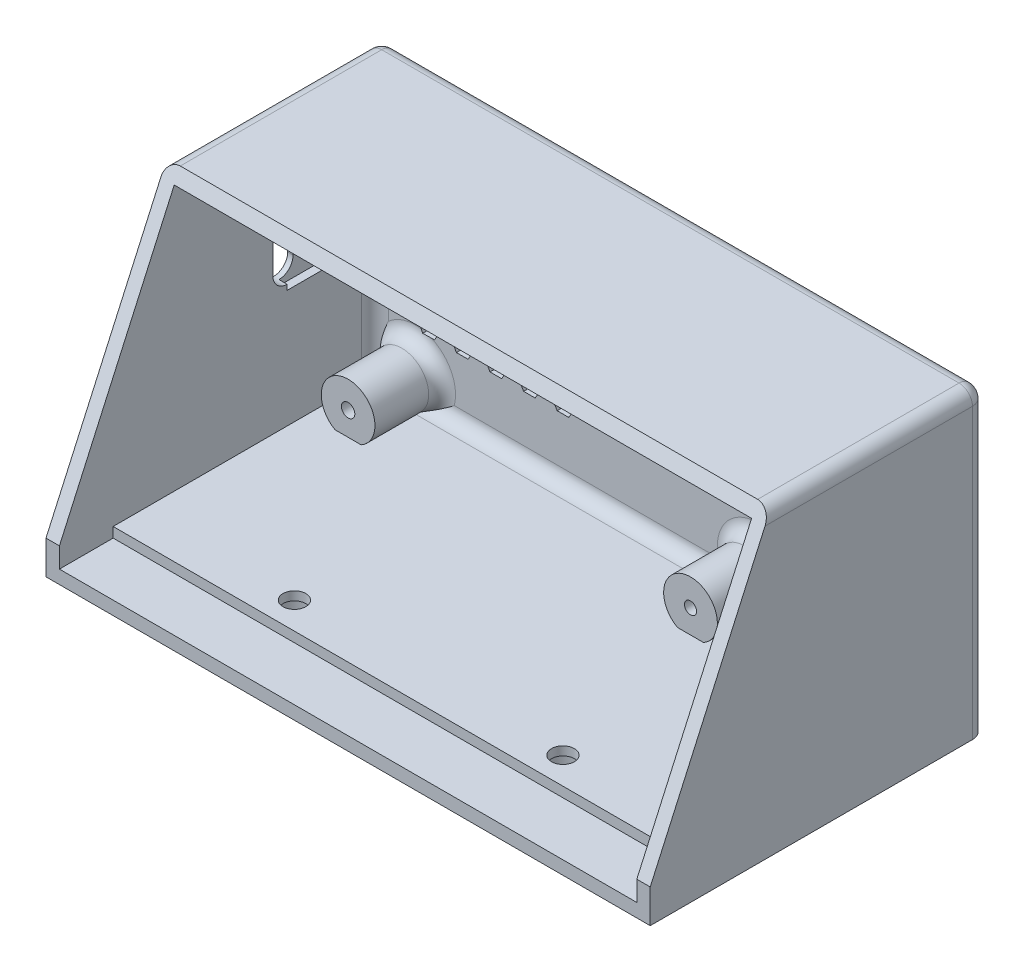
SolidWorks part; units mm, degrees
ref_plane "前视基准面" through (0, 0, 0) normal (0, 0, 1) x (1, 0, 0)
ref_plane "上视基准面" through (0, 0, 0) normal (0, 1, 0) x (1, 0, 0)
ref_plane "右视基准面" through (0, 0, 0) normal (1, 0, 0) x (0, 0, -1)
sketch "草图1" plane through (0, 0, 0) normal (0, 0, 1) x (1, 0, 0)
  line L1 (0, 0) -> (90, 0)
  line L2 (0, 0) -> (0, 45)
  line L3 (0, 45) -> (90, 45)
  line L4 (90, 0) -> (90, 45)
  dimension "D1" = 90
  dimension "D2" = 45
extrude "凸台-拉伸1" add sketch "草图1" along normal blind 50
sketch "草图2" plane through (90, 0, 0) normal (1, 0, 0) x (0, 0, -1)
  line L0 (-32, 45) -> (-50, 5)
  line L1 (-50, 45) -> (0, 45) construction
  line L2 (-50, 0) -> (-50, 45) construction
  line L3 (-50, 5) -> (-50, 45)
  line L4 (-50, 45) -> (-32, 45)
  dimension "D1" = 18
  dimension "D2" = 40
extrude "切除-拉伸1" cut sketch "草图2" against normal through all
ref_plane "基准面1" through (0, 0, 70) normal (0, 0, 1) x (1, 0, 0)
sketch "草图3" plane through (0, 0, 70) normal (0, 0, 1) x (1, 0, 0)
  line L0 (0, 5) -> (0, 45) construction
  line L1 (2, 2) -> (88, 2)
  line L2 (2, 2) -> (2, 43)
  line L3 (2, 43) -> (88, 43)
  line L4 (88, 2) -> (88, 43)
  line L5 (0, 45) -> (90, 45) construction
  line L6 (0, 0) -> (90, 0) construction
  line L7 (90, 5) -> (90, 45) construction
  dimension "D1" = 2
  dimension "D2" = 2
  dimension "D3" = 2
  dimension "D4" = 2
extrude "切除-拉伸2" cut sketch "草图3" against normal offset from surface (67 mm away) 3 up to face at (45, 22.5, 0)
sketch "草图4" plane through (0, 0, 3) normal (0, 0, 1) x (1, 0, 0)
  line L0 (2, 2) -> (88, 2) construction
  line L1 (2, 5) -> (2, 43) construction
  circle A0 centre (8, 38) radius 4
  circle A1 centre (59, 38) radius 4
  circle A2 centre (8, 7) radius 4
  circle A3 centre (59, 7) radius 4
  dimension "D1" = 8
  dimension "D2" = 8
  dimension "D3" = 8
  dimension "D4" = 8
  dimension "D5" = 51
  dimension "D6" = 31
  dimension "D7" = 5
  dimension "D8" = 6
extrude "凸台-拉伸2" add sketch "草图4" along normal blind 10
sketch "草图5" plane through (0, 0, 13) normal (0, 0, 1) x (1, 0, 0)
  circle A0 centre (8, 38) radius 0.9
  circle A1 centre (59, 38) radius 1
  circle A2 centre (8, 7) radius 1
  circle A3 centre (59, 7) radius 0.9
  dimension "D1" = 1.8
  dimension "D2" = 2
  dimension "D3" = 1.8
  dimension "D4" = 2
extrude "切除-拉伸3" cut sketch "草图5" against normal blind 7
ref_plane "基准面2" through (0, 0, 9) normal (0, 0, 1) x (1, 0, 0)
sketch "草图6" plane through (0, 0, 9) normal (0, 0, 1) x (1, 0, 0)
  circle A0 centre (8, 38) radius 2.5
  circle A1 centre (59, 38) radius 2.5
  circle A2 centre (8, 7) radius 2.5
  circle A3 centre (59, 7) radius 2.5
  dimension "D1" = 5
  dimension "D2" = 5
  dimension "D3" = 5
  dimension "D4" = 5
sketch "草图7" plane through (0, 0, 0) normal (-1, 0, 0) x (0, 0, 1)
  line L0 (16.1, 30.1) -> (16.1, 23.9) construction
  line L1 (18.2, 30.1) -> (18.2, 23.9)
  line L2 (14, 30.1) -> (14, 23.9)
  line L3 (0, 45) -> (0, 0) construction
  line L4 (32, 45) -> (0, 45) construction
  arc A0 (18.2, 30.1) -> (14, 30.1) centre (16.1, 30.1) ccw
  arc A1 (14, 23.9) -> (18.2, 23.9) centre (16.1, 23.9) ccw
  point P2 (16.1, 27)
  dimension "D1" = 6.2
  dimension "D2" = 4.2
  dimension "D3" = 16.1
  dimension "D4" = 18
extrude "切除-拉伸5" cut sketch "草图7" against normal up to surface (2 mm away) up to face at (2, 19, 27.78)
sketch "草图8" plane through (2, 0, 0) normal (1, 0, 0) x (0, 0, -1)
  line L0 (-3, 43) -> (-3, 2) construction
  line L1 (-16.1, 33) -> (-3, 33)
  line L2 (-16.1, 33) -> (-16.1, 21)
  line L3 (-16.1, 21) -> (-3, 21)
  line L4 (-3, 33) -> (-3, 21)
  line L5 (-14, 23.9) -> (-14, 30.1) construction
  arc A0 (-14, 30.1) -> (-18.2, 30.1) centre (-16.1, 30.1) ccw construction
  point P9 (-16.1, 32.2)
  point P12 (-14, 27)
  point P13 (-16.1, 27)
  dimension "D1" = 12
extrude "切除-拉伸6" cut sketch "草图8" against normal blind 1.2
sketch "草图9" plane through (0, 0, 0) normal (0, 0, -1) x (-1, 0, 0)
  line L0 (-90, 45) -> (0, 45) construction
  line L1 (-8.2679, 29) -> (-9.134, 30.5)
  line L2 (-9.134, 30.5) -> (-10.866, 30.5)
  line L3 (-10.866, 30.5) -> (-11.7321, 29)
  line L4 (-11.7321, 29) -> (-10.866, 27.5)
  line L5 (-10.866, 27.5) -> (-9.134, 27.5)
  line L6 (-9.134, 27.5) -> (-8.2679, 29)
  line L9 (-14.134, 30.5) -> (-15.866, 30.5)
  line L10 (-13.2679, 29) -> (-14.134, 30.5)
  line L11 (-14.134, 27.5) -> (-13.2679, 29)
  line L12 (-15.866, 27.5) -> (-14.134, 27.5)
  line L13 (-16.7321, 29) -> (-15.866, 27.5)
  line L14 (-15.866, 30.5) -> (-16.7321, 29)
  line L15 (-19.134, 30.5) -> (-20.866, 30.5)
  line L16 (-18.2679, 29) -> (-19.134, 30.5)
  line L17 (-19.134, 27.5) -> (-18.2679, 29)
  line L18 (-20.866, 27.5) -> (-19.134, 27.5)
  line L19 (-21.7321, 29) -> (-20.866, 27.5)
  line L20 (-20.866, 30.5) -> (-21.7321, 29)
  line L21 (-24.134, 30.5) -> (-25.866, 30.5)
  line L22 (-23.2679, 29) -> (-24.134, 30.5)
  line L23 (-24.134, 27.5) -> (-23.2679, 29)
  line L24 (-25.866, 27.5) -> (-24.134, 27.5)
  line L25 (-26.7321, 29) -> (-25.866, 27.5)
  line L26 (-25.866, 30.5) -> (-26.7321, 29)
  line L27 (-29.134, 30.5) -> (-30.866, 30.5)
  line L28 (-28.2679, 29) -> (-29.134, 30.5)
  line L29 (-29.134, 27.5) -> (-28.2679, 29)
  line L30 (-30.866, 27.5) -> (-29.134, 27.5)
  line L31 (-31.7321, 29) -> (-30.866, 27.5)
  line L32 (-30.866, 30.5) -> (-31.7321, 29)
  line L39 (0, 45) -> (0, 0) construction
  line L40 (-8.2679, 24) -> (-9.134, 25.5)
  line L41 (-9.134, 25.5) -> (-10.866, 25.5)
  line L42 (-10.866, 25.5) -> (-11.7321, 24)
  line L43 (-11.7321, 24) -> (-10.866, 22.5)
  line L44 (-10.866, 22.5) -> (-9.134, 22.5)
  line L45 (-9.134, 22.5) -> (-8.2679, 24)
  line L46 (-14.134, 25.5) -> (-15.866, 25.5)
  line L47 (-13.2679, 24) -> (-14.134, 25.5)
  line L48 (-14.134, 22.5) -> (-13.2679, 24)
  line L49 (-15.866, 22.5) -> (-14.134, 22.5)
  line L50 (-16.7321, 24) -> (-15.866, 22.5)
  line L51 (-15.866, 25.5) -> (-16.7321, 24)
  line L52 (-19.134, 25.5) -> (-20.866, 25.5)
  line L53 (-18.2679, 24) -> (-19.134, 25.5)
  line L54 (-19.134, 22.5) -> (-18.2679, 24)
  line L55 (-20.866, 22.5) -> (-19.134, 22.5)
  line L56 (-21.7321, 24) -> (-20.866, 22.5)
  line L57 (-20.866, 25.5) -> (-21.7321, 24)
  line L58 (-24.134, 25.5) -> (-25.866, 25.5)
  line L59 (-23.2679, 24) -> (-24.134, 25.5)
  line L60 (-24.134, 22.5) -> (-23.2679, 24)
  line L61 (-25.866, 22.5) -> (-24.134, 22.5)
  line L62 (-26.7321, 24) -> (-25.866, 22.5)
  line L63 (-25.866, 25.5) -> (-26.7321, 24)
  line L64 (-29.134, 25.5) -> (-30.866, 25.5)
  line L65 (-28.2679, 24) -> (-29.134, 25.5)
  line L66 (-29.134, 22.5) -> (-28.2679, 24)
  line L67 (-30.866, 22.5) -> (-29.134, 22.5)
  line L68 (-31.7321, 24) -> (-30.866, 22.5)
  line L69 (-30.866, 25.5) -> (-31.7321, 24)
  line L70 (-8.2679, 19) -> (-9.134, 20.5)
  line L71 (-9.134, 20.5) -> (-10.866, 20.5)
  line L72 (-10.866, 20.5) -> (-11.7321, 19)
  line L73 (-11.7321, 19) -> (-10.866, 17.5)
  line L74 (-10.866, 17.5) -> (-9.134, 17.5)
  line L75 (-9.134, 17.5) -> (-8.2679, 19)
  line L76 (-14.134, 20.5) -> (-15.866, 20.5)
  line L77 (-13.2679, 19) -> (-14.134, 20.5)
  line L78 (-14.134, 17.5) -> (-13.2679, 19)
  line L79 (-15.866, 17.5) -> (-14.134, 17.5)
  line L80 (-16.7321, 19) -> (-15.866, 17.5)
  line L81 (-15.866, 20.5) -> (-16.7321, 19)
  line L82 (-19.134, 20.5) -> (-20.866, 20.5)
  line L83 (-18.2679, 19) -> (-19.134, 20.5)
  line L84 (-19.134, 17.5) -> (-18.2679, 19)
  line L85 (-20.866, 17.5) -> (-19.134, 17.5)
  line L86 (-21.7321, 19) -> (-20.866, 17.5)
  line L87 (-20.866, 20.5) -> (-21.7321, 19)
  line L88 (-24.134, 20.5) -> (-25.866, 20.5)
  line L89 (-23.2679, 19) -> (-24.134, 20.5)
  line L90 (-24.134, 17.5) -> (-23.2679, 19)
  line L91 (-25.866, 17.5) -> (-24.134, 17.5)
  line L92 (-26.7321, 19) -> (-25.866, 17.5)
  line L93 (-25.866, 20.5) -> (-26.7321, 19)
  line L94 (-29.134, 20.5) -> (-30.866, 20.5)
  line L95 (-28.2679, 19) -> (-29.134, 20.5)
  line L96 (-29.134, 17.5) -> (-28.2679, 19)
  line L97 (-30.866, 17.5) -> (-29.134, 17.5)
  line L98 (-31.7321, 19) -> (-30.866, 17.5)
  line L99 (-30.866, 20.5) -> (-31.7321, 19)
  line L100 (-8.2679, 14) -> (-9.134, 15.5)
  line L101 (-9.134, 15.5) -> (-10.866, 15.5)
  line L102 (-10.866, 15.5) -> (-11.7321, 14)
  line L103 (-11.7321, 14) -> (-10.866, 12.5)
  line L104 (-10.866, 12.5) -> (-9.134, 12.5)
  line L105 (-9.134, 12.5) -> (-8.2679, 14)
  line L106 (-14.134, 15.5) -> (-15.866, 15.5)
  line L107 (-13.2679, 14) -> (-14.134, 15.5)
  line L108 (-14.134, 12.5) -> (-13.2679, 14)
  line L109 (-15.866, 12.5) -> (-14.134, 12.5)
  line L110 (-16.7321, 14) -> (-15.866, 12.5)
  line L111 (-15.866, 15.5) -> (-16.7321, 14)
  line L112 (-19.134, 15.5) -> (-20.866, 15.5)
  line L113 (-18.2679, 14) -> (-19.134, 15.5)
  line L114 (-19.134, 12.5) -> (-18.2679, 14)
  line L115 (-20.866, 12.5) -> (-19.134, 12.5)
  line L116 (-21.7321, 14) -> (-20.866, 12.5)
  line L117 (-20.866, 15.5) -> (-21.7321, 14)
  line L118 (-24.134, 15.5) -> (-25.866, 15.5)
  line L119 (-23.2679, 14) -> (-24.134, 15.5)
  line L120 (-24.134, 12.5) -> (-23.2679, 14)
  line L121 (-25.866, 12.5) -> (-24.134, 12.5)
  line L122 (-26.7321, 14) -> (-25.866, 12.5)
  line L123 (-25.866, 15.5) -> (-26.7321, 14)
  line L124 (-29.134, 15.5) -> (-30.866, 15.5)
  line L125 (-28.2679, 14) -> (-29.134, 15.5)
  line L126 (-29.134, 12.5) -> (-28.2679, 14)
  line L127 (-30.866, 12.5) -> (-29.134, 12.5)
  line L128 (-31.7321, 14) -> (-30.866, 12.5)
  line L129 (-30.866, 15.5) -> (-31.7321, 14)
  circle A0 centre (-10, 29) radius 1.5 construction
  circle A1 centre (-15, 29) radius 1.5 construction
  circle A2 centre (-20, 29) radius 1.5 construction
  circle A3 centre (-25, 29) radius 1.5 construction
  circle A4 centre (-30, 29) radius 1.5 construction
  circle A5 centre (-10, 24) radius 1.5 construction
  circle A6 centre (-15, 24) radius 1.5 construction
  circle A7 centre (-20, 24) radius 1.5 construction
  circle A8 centre (-25, 24) radius 1.5 construction
  circle A9 centre (-30, 24) radius 1.5 construction
  circle A10 centre (-10, 19) radius 1.5 construction
  circle A11 centre (-15, 19) radius 1.5 construction
  circle A12 centre (-20, 19) radius 1.5 construction
  circle A13 centre (-25, 19) radius 1.5 construction
  circle A14 centre (-30, 19) radius 1.5 construction
  circle A15 centre (-10, 14) radius 1.5 construction
  circle A16 centre (-15, 14) radius 1.5 construction
  circle A17 centre (-20, 14) radius 1.5 construction
  circle A18 centre (-25, 14) radius 1.5 construction
  circle A19 centre (-30, 14) radius 1.5 construction
  dimension "D1" = 3
  dimension "D2" = 16
  dimension "D3" = 10
  dimension "D4" = 5
  dimension "D5" = 4
extrude "切除-拉伸7" cut sketch "草图9" against normal up to surface (3 mm away) up to face at (55, 7, 3)
sketch "草图10" plane through (0, 0, 3) normal (0, 0, 1) x (1, 0, 0)
  line L0 (20.866, 30.5) -> (19.134, 30.5) construction
  line L1 (88, 43) -> (2, 43) construction
  circle A0 centre (20, 36.8) radius 4.5
  circle A1 centre (20, 36.8) radius 3.5
  point P6 (20, 30.5)
  dimension "D1" = 9
  dimension "D2" = 7
  dimension "D3" = 6.2
extrude "凸台-拉伸3" add sketch "草图10" along normal blind 3
sketch "草图11" plane through (0, 0, 3) normal (0, 0, 1) x (1, 0, 0)
  circle A0 centre (20, 36.8) radius 2
  dimension "D1" = 4
extrude "切除-拉伸8" cut sketch "草图11" against normal through all
sketch "草图13" plane through (0, 2, 0) normal (0, 1, 0) x (1, 0, 0)
  line L0 (88, -3) -> (88, -50) construction
  line L1 (2, -3) -> (88, -3)
  line L2 (2, -3) -> (2, -42)
  line L3 (2, -42) -> (88, -42)
  line L4 (88, -3) -> (88, -42)
  line L5 (88, -50) -> (2, -50) construction
  dimension "D1" = 8
extrude "凸台-拉伸5" add sketch "草图13" along normal blind 1.5
sketch "草图12" plane through (0, 0, 0) normal (0, -1, 0) x (1, 0, 0)
  line L0 (45, 50) -> (45, -10.3613) construction
  line L1 (0, 50) -> (90, 50) construction
  circle A0 centre (25, 38) radius 1.7
  circle A1 centre (65, 38) radius 1.7
  dimension "D1" = 3.4
  dimension "D3" = 12
  dimension "D2" = 20
extrude "切除-拉伸9" cut sketch "草图12" against normal up to next
sketch "草图14" plane through (0, 0, 0) normal (0, -1, 0) x (1, 0, 0)
  circle A0 centre (25, 38) radius 3.1
  circle A1 centre (65, 38) radius 3.1
  dimension "D1" = 6.2
  dimension "D2" = 6.2
extrude "切除-拉伸10" cut sketch "草图14" against normal blind 2.2
fillet "圆角2" radius 2 5 edges at (0, 22.5, 0) (90, 22.5, 0) (45, 45, 0) (90, 45, 16) (0, 45, 16)
fillet "圆角3" radius 2 11 edges at (2, 38, 3) (2, 12.25, 3) (33.5, 3.5, 3) (74.4682, 3.5, 3) (88, 23.25, 3) (45, 43, 3) (8, 11, 3) (59, 11, 3) (55, 38, 3) (15.5, 36.8, 3) (4, 38, 3)
